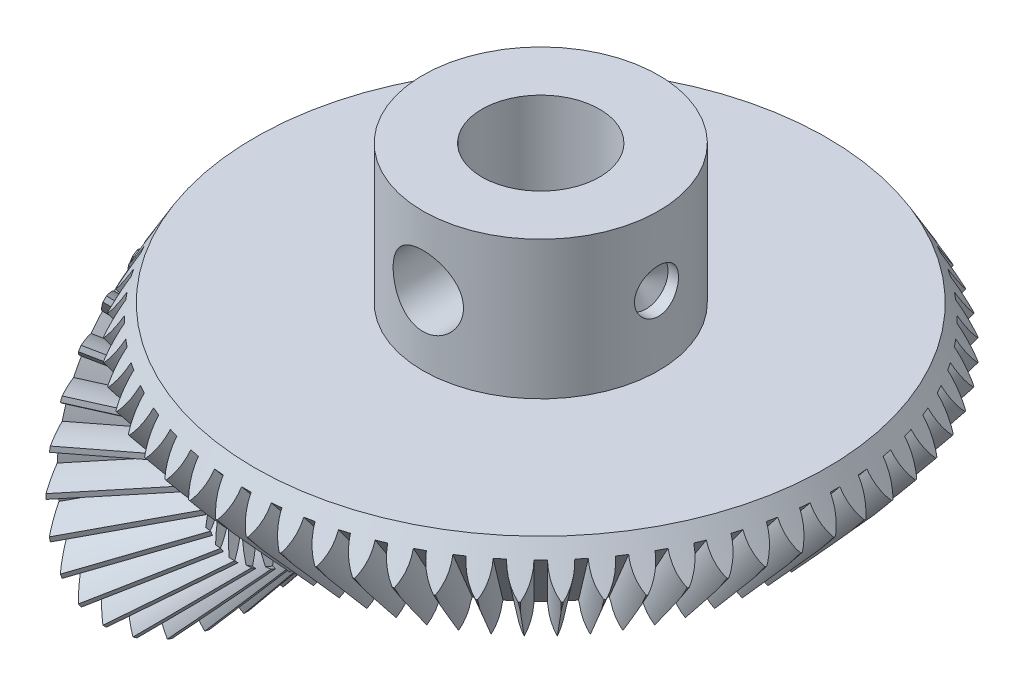
SolidWorks part; units mm, degrees
ref_plane "Front Plane" through (0, 0, 0) normal (0, 0, 1) x (1, 0, 0)
ref_plane "Top Plane" through (0, 0, 0) normal (0, 1, 0) x (1, 0, 0)
ref_plane "Right Plane" through (0, 0, 0) normal (1, 0, 0) x (0, 0, -1)
sketch "Sketch1" plane through (0, 0, 0) normal (0, 0, 1) x (1, 0, 0)
  line L0 (-4.7625, 14.2748) -> (-2.3787, 14.2748)
  line L1 (-2.3787, 14.2748) -> (-2.3787, 4.6228)
  line L2 (-19.05, 2.3787) -> (-19.05, 4.7625)
  line L3 (-19.05, 4.7625) -> (-13.462, 4.7625)
  line L4 (0, 19.9421) -> (0, -19.9421) construction
  line L5 (-20.2254, 0) -> (20.2254, 0) construction
  line L6 (-19.05, 2.3787) -> (-10.2922, 2.3787)
  line L7 (0, 0) -> (-12.4337, 7.1786) construction
  line L8 (0, 0) -> (15.0111, 8.6667) construction
  line L9 (-4.7625, 14.2748) -> (-4.7625, 8.6868)
  line L10 (-4.7625, 8.6868) -> (-11.5629, 8.6868)
  line L13 (-9.2166, 4.6228) -> (-2.3787, 4.6228)
  line L14 (-16.256, 5.1537) -> (-16.256, 2.4592) construction
  line L15 (-12.4337, 7.1786) -> (-12.4337, -7.1786) construction
  line L16 (-12.4337, -7.1786) -> (0, 0) construction
  line L17 (-12.5125, 7.0422) -> (-9.7544, 3.6913) construction
  line L18 (-13.462, 4.7625) -> (-13.462, 5.3975)
  line L19 (-13.462, 5.3975) -> (-11.5629, 8.6868)
  line L20 (-10.2922, 2.3787) -> (-10.2922, 2.7597)
  line L21 (-10.2922, 2.7597) -> (-9.2166, 4.6228)
  point P2 (-8.9142, 5.1466)
  dimension "Length [YY]" = 14.2748
  dimension "Length [XX]" = 19.05
  dimension "Bore [BOR]" = 4.7574
  dimension "D1" = 4.7574
  dimension "D2" = 30
  dimension "D3" = 9.525
  dimension "Diameter [SD4]" = 9.525
  dimension "D4" = 2.794
  dimension "D6" = 5.588
  dimension "D8" = 2.3838
  dimension "D7" = 4.064
  dimension "D9" = 0.635
  dimension "D10" = 60
  dimension "D5" = 4.064
  dimension "D11" = 0.381
sketch "Sketch2" plane through (0, 0, 0) normal (0, 0, 1) x (1, 0, 0)
  line L0 (-4.7625, 14.2748) -> (-2.3787, 14.2748) construction
  line L1 (-4.7625, 14.2748) -> (-4.7625, 8.6868) construction
  line L2 (-4.7625, 8.6868) -> (-11.5629, 8.6868) construction
  line L3 (-2.3787, 14.2748) -> (-2.3787, 4.6228) construction
  line L4 (-9.2166, 4.6228) -> (-2.3787, 4.6228) construction
  line L6 (-12.5125, 7.0422) -> (-9.7544, 3.6913) construction
  line L8 (-4.7625, 14.2748) -> (-2.3787, 14.2748)
  line L9 (-4.7625, 14.2748) -> (-4.7625, 8.6868)
  line L10 (-4.7625, 8.6868) -> (-11.5629, 8.6868)
  line L11 (-2.3787, 14.2748) -> (-2.3787, 4.6228)
  line L12 (-9.2166, 4.6228) -> (-2.3787, 4.6228)
  line L13 (-9.7544, 3.6913) -> (-9.2166, 4.6228)
  line L14 (-12.5125, 7.0422) -> (-9.7544, 3.6913)
  line L15 (-11.5629, 8.6868) -> (-12.5125, 7.0422)
  line L16 (0, 19.9421) -> (0, -19.9421) construction
  line L17 (0, 19.9421) -> (0, -19.9421) construction
revolve "Revolve1-LargestGear" add sketch "Sketch2" angle 360 about L17
ref_plane "Plane1" through (-9.7544, 3.6913, 0) normal (0.6355, -0.7721, 0) x (0.7721, 0.6355, 0)
sketch "Sketch3" plane through (-9.7544, 3.6913, 0) normal (0.6355, -0.7721, 0) x (0.7721, 0.6355, 0)
  line L0 (1.143, 0) -> (0, 0) construction
  line L1 (13.208, 0) -> (0.5118, -0.3117) construction
  line L2 (0.5118, 0.3117) -> (0.873, 0.1802) construction
  line L3 (0.5118, 0.3117) -> (13.208, 0) construction
  line L4 (1.1446, 0.1948) -> (0.5097, 0.2051) construction
  line L5 (1.1446, 0.1948) -> (1.1366, -0.2963) construction
  line L6 (0, 0) -> (-0.254, 0) construction
  circle A0 centre (13.208, 0) radius 13.208 construction
  circle A1 centre (13.208, 0) radius 12.7 construction
  circle A2 centre (13.208, 0) radius 12.065 construction
  arc A3 (-0.2304, 0.7974) -> (1.1446, 0.1948) centre (1.1759, 2.1363) ccw
  arc A4 (-0.2304, -0.7974) -> (1.1446, -0.1948) centre (1.1759, -2.1363) cw
  arc A5 (1.1446, 0.1948) -> (1.1446, -0.1948) centre (13.208, 0) ccw
  arc A6 (-0.2304, 0.7974) -> (-0.2304, -0.7974) centre (13.208, 0) ccw
  ellipse E0 centre (7.5314, 0) end of major axis (7.5314, -9.7544) minor radius 7.5314 construction
  ellipse E1 centre (9.6609, 0) end of major axis (9.6609, -12.5125) minor radius 9.6609 construction
  ellipse E2 centre (9.6609, 0) end of major axis (9.6609, -12.5125) minor radius 9.6609 (0.0179, 0.7623) -> (0.0179, -0.7623) ccw construction
  dimension "Dimension [SD21]" = 26.416
  dimension "Pitch Diameter Largest Gear [PD1]" = 25.4
  dimension "D2" = 1.143
  dimension "D3" = 2.813
  dimension "D4" = 20
  dimension "D5" = 0.254
extrude "Cut-Extrude3-Teeth" cut sketch "Sketch3" against normal blind 10 and the other way through all
pattern_circular "CirPattern1" count 64 over 360 about axis through (0, 19.9421, 0) along (0, -1, 0) of "Cut-Extrude3-Teeth"
sketch "Sketch4" plane through (0, 0, 0) normal (0, 0, 1) x (1, 0, 0)
  line L0 (-20.2254, 0) -> (20.2254, 0) construction
  line L1 (-20.2254, 0) -> (20.2254, 0) construction
  line L2 (-12.5125, 7.0422) -> (-9.7544, 3.6913) construction
  line L3 (-12.5125, 7.0422) -> (-9.7544, 3.6913)
  line L4 (-13.462, 5.3975) -> (-11.5629, 8.6868) construction
  line L5 (-13.462, 4.7625) -> (-13.462, 5.3975) construction
  line L6 (-13.462, 5.3975) -> (-12.5125, 7.0422)
  line L7 (-13.462, 4.7625) -> (-13.462, 5.3975)
  line L8 (-10.2922, 2.7597) -> (-9.2166, 4.6228) construction
  line L10 (-19.05, 2.3787) -> (-10.2922, 2.3787) construction
  line L11 (-19.05, 2.3787) -> (-19.05, 4.7625) construction
  line L12 (-19.05, 4.7625) -> (-13.462, 4.7625) construction
  line L13 (-10.2922, 2.3787) -> (-10.2922, 2.7597) construction
  line L14 (-10.2922, 2.7597) -> (-9.7544, 3.6913)
  line L15 (-10.2922, 2.3787) -> (-10.2922, 2.7597)
  line L20 (-19.05, 2.3787) -> (-10.2922, 2.3787)
  line L21 (-19.05, 2.3787) -> (-19.05, 4.7625)
  line L22 (-19.05, 4.7625) -> (-13.462, 4.7625)
revolve "Revolve2-SmallestGear" add sketch "Sketch4" angle 360 about L1
sketch "Sketch5" plane through (-9.7544, 3.6913, 0) normal (0.6355, -0.7721, 0) x (0.7721, 0.6355, 0)
  line L0 (5.1856, 0) -> (0.0431, 0) construction
  line L1 (-1.7783, 0) -> (1.7783, 0) construction
  arc A0 (-1.2494, 0) -> (1.1426, 0.1016) centre (0.049, -2.3589) cw
  arc A1 (1.1426, 0.1016) -> (1.1426, -0.1016) centre (-10.922, 0) cw
  arc A2 (1.1426, -0.1016) -> (-1.2494, 0) centre (0.049, 2.3589) cw
  arc A5 (1.009, -0.2018) -> (0.1718, -0.4744) centre (1.1759, -2.1363) ccw construction
  arc A6 (1.1446, 0.1948) -> (1.1446, -0.1948) centre (13.208, 0) ccw construction
  arc A8 (0.1718, 0.4744) -> (1.009, 0.2018) centre (1.1759, 2.1363) ccw construction
  ellipse E0 centre (-2.7611, 0) end of major axis (-2.7611, 2.3787) minor radius 1.5117 construction
  point P24 (1.143, 0)
  dimension "D1" = 0.2032
extrude "Extrude1-Teeth" add sketch "Sketch5" against normal blind 5.842 and the other way blind 2.54
pattern_circular "CirPattern2" count 32 over 360 about axis through (-20.2254, 0, 0) along (1, 0, 0) of "Extrude1-Teeth"
sketch "Sketch6" plane through (0, 0, 0) normal (0, 0, 1) x (1, 0, 0)
  line L0 (-13.462, 4.7625) -> (-13.462, 5.3975) construction
  line L1 (-19.05, 4.7625) -> (-13.462, 4.7625) construction
  line L2 (-10.2922, 2.3787) -> (-10.2922, 2.7597) construction
  line L3 (-4.7625, 8.6868) -> (-11.5629, 8.6868) construction
  line L4 (-4.7625, 14.2748) -> (-4.7625, 8.6868) construction
  line L5 (-13.462, 4.7625) -> (-13.462, 5.3975)
  line L6 (-13.462, 5.3975) -> (-11.5629, 8.6868) construction
  line L7 (-9.2166, 4.6228) -> (-2.3787, 4.6228) construction
  line L9 (-19.05, 2.3787) -> (-10.2922, 2.3787) construction
  line L10 (-20.2254, 0) -> (20.2254, 0) construction
  line L11 (-19.05, 4.7625) -> (-13.462, 4.7625)
  line L12 (-13.462, 5.3975) -> (-11.5629, 8.6868)
  line L13 (-4.7625, 8.6868) -> (-11.5629, 8.6868)
  line L14 (-4.7625, 11.4808) -> (-4.7625, 8.6868)
  line L15 (-19.05, 2.3787) -> (-19.05, 0)
  line L16 (0, 0) -> (0, 4.6228)
  line L17 (-9.2166, 4.6228) -> (0, 4.6228)
  line L19 (-19.05, 2.3787) -> (-10.2922, 2.3787)
  line L20 (-20.2254, 0) -> (20.2254, 0) construction
  line L21 (-19.05, 4.7625) -> (-19.05, 11.4808)
  line L22 (-19.05, 11.4808) -> (-4.7625, 11.4808)
  line L23 (-19.05, 0) -> (0, 0)
  line L24 (-19.05, 4.7625) -> (-19.05, -4.7625) construction
  line L25 (0, 19.9421) -> (0, -19.9421) construction
  line L26 (-10.2922, 2.7597) -> (-9.2166, 4.6228) construction
  line L27 (-10.2922, 2.3787) -> (-10.2922, 2.7597)
  line L28 (-10.2922, 2.7597) -> (-9.2166, 4.6228)
revolve "Cut-Revolve1" cut sketch "Sketch6" angle 360 about L20
ref_plane "Plane2" through (0, 0, 2.54) normal (0, 0, 1) x (1, 0, 0)
hole_wizard "#4-40 Tapped Hole1" positions "Sketch11" profile "Sketch10" tap size "#4-40" standard "Ansi Inch"
sketch "Sketch11" plane through (0, 0, 2.54) normal (0, 0, 1) x (1, 0, 0)
  line L0 (4.7625, 14.2748) -> (-4.7625, 14.2748) construction
  point P0 (0, 11.4808)
  dimension "D1" = 2.794
sketch "Sketch10" plane through (0, 11.4808, 2.54) normal (1, 0, 0) x (0, 1, 0)
  line L0 (0, 0) -> (0, 4.4892)
  line L1 (0, 4.4892) -> (1.1303, 3.81)
  line L2 (1.1303, 3.81) -> (1.1303, 3.175)
  line L3 (1.1303, 3.175) -> (1.4224, 3.175)
  line L4 (1.4224, 3.175) -> (1.4224, 0)
  line L5 (1.4224, 0) -> (0, 0)
  line L10 (0, 4.4892) -> (-1.1303, 3.81) construction
  line L11 (0, -6.35) -> (0, 107.95) construction
  dimension "Tap Drill Dia." = 2.2606
  dimension "Tap Drill Depth" = 3.81
  dimension "Thread Major Dia." = 2.8448
  dimension "Thread Depth" = 3.175
  dimension "Drill Angle" = 118
ref_plane "Plane3" through (4.7625, 0, 0) normal (1, 0, 0) x (0, 0, -1)
hole_wizard "#50 (0.07) Diameter Hole1" positions "Sketch13" profile "Sketch12" hole size "#50" standard "Ansi Inch"
sketch "Sketch13" plane through (4.7625, 0, 0) normal (1, 0, 0) x (0, 0, -1)
  line L0 (2.3787, 14.2748) -> (-2.3787, 14.2748) construction
  point P0 (0, 11.4808)
  dimension "D1" = 2.794
sketch "Sketch12" plane through (4.7625, 11.4808, 0) normal (0, 1, 0) x (0, 0, -1)
  line L0 (0, 0) -> (0, 1.0422)
  line L1 (0, 1.0422) -> (0.889, 0.508)
  line L2 (0.889, 0.508) -> (0.889, 0)
  line L5 (0.889, 0) -> (0, 0)
  line L10 (0, 1.0422) -> (-0.889, 0.508) construction
  line L11 (0, -6.35) -> (0, 107.95) construction
  dimension "Hole Dia." = 1.778
  dimension "Hole Depth" = 0.508
  dimension "Drill Angle" = 118
sketch "Sketch14" plane through (-19.05, 0, 0) normal (-1, 0, 0) x (0, 0, 1)
  circle A0 centre (0, 0) radius 6.6835
extrude "Cut-Extrude1" cut sketch "Sketch14" against normal blind 5.588
equation "\"D1@Sketch1\" = \"Bore [BOR]@Sketch1\""
equation "\"D3@Sketch1\" = \"Diameter [SD4]@Sketch1\""
equation "\"D2@Sketch3\" = (\"Dimension [SD21]@Sketch3\"-\"Pitch Diameter Largest Gear [PD1]@Sketch3\")*1.125"
equation "\"D3@Sketch3\" = 180/\"Number of Teeth Largest Gear [NOF1]@CirPattern1\""
